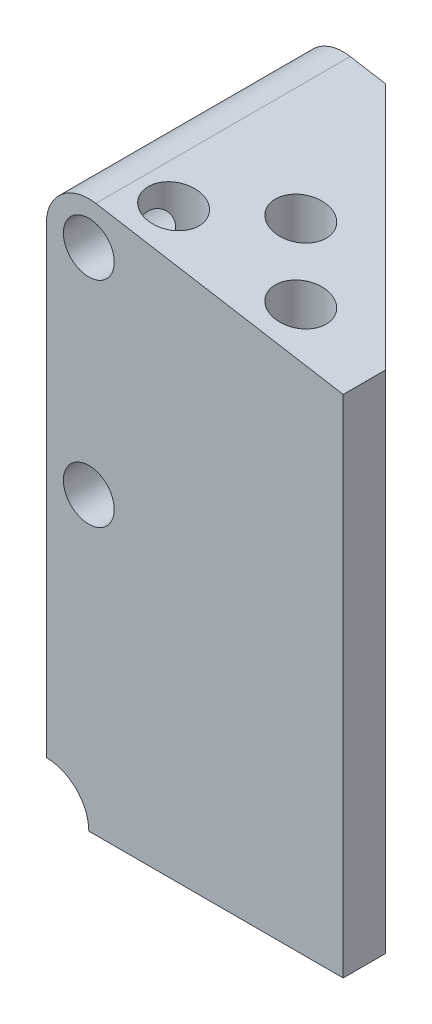
SolidWorks part; units mm, degrees
ref_plane "Front Plane" through (0, 0, 0) normal (0, 0, 1) x (1, 0, 0)
ref_plane "Top Plane" through (0, 0, 0) normal (0, 1, 0) x (1, 0, 0)
ref_plane "Right Plane" through (0, 0, 0) normal (1, 0, 0) x (0, 0, -1)
sketch "Sketch1" plane through (0, 0, 0) normal (0, 0, 1) x (1, 0, 0)
  line L0 (0, 0) -> (0, 68.7065) construction
  line L1 (-10, 130) -> (10, 130)
  line L2 (-10, 130) -> (-10, 0)
  line L3 (-10, 0) -> (10, 0)
  line L4 (10, 130) -> (10, 0)
  line L7 (0, 68.7065) -> (0, 119.2065) construction
  circle A0 centre (0, 119.2065) radius 2.5
  circle A1 centre (0, 68.7065) radius 2.5
  dimension "D2" = 5
  dimension "D3" = 68.7065
  dimension "D1" = 50.5
  dimension "D4" = 20
  dimension "D5" = 130
extrude "Boss-Extrude1" add sketch "Sketch1" along normal blind 60
sketch "Sketch2" plane through (0, 130, 0) normal (0, 1, 0) x (1, 0, 0)
  line L0 (10, 0) -> (60, -50)
  line L2 (10, -60) -> (10, 0)
  line L3 (10, -60) -> (60, -60)
  line L4 (60, -60) -> (60, -50)
  dimension "D1" = 45
  dimension "D2" = 10
extrude "Boss-Extrude2" add sketch "Sketch2" against normal up to surface (130 mm away) up to face at (0, 0, 30)
sketch "Sketch4" plane through (0, 0, 0) normal (0, 0, -1) x (-1, 0, 0)
  line L0 (-10, 68.7065) -> (-60, 68.7065)
  line L1 (10, 0) -> (10, 68.7065)
  line L2 (-10, 0) -> (10, 0)
  line L4 (-10, 130) -> (10, 130)
  line L5 (10, 130) -> (10, 119.2065)
  line L6 (10, 130) -> (10, 0) construction
  line L7 (-60, 0) -> (-60, 130) construction
  line L8 (-60, 68.7065) -> (-60, 0)
  line L9 (-60, 0) -> (-10, 0)
  line L10 (-10, 119.2065) -> (-60, 119.2065)
  line L11 (-60, 119.2065) -> (-60, 130)
  line L12 (-60, 130) -> (-10, 130)
  line L13 (-1.6667, 129.0666) -> (-60, 119.2065)
  line L14 (-1.6667, 58.8463) -> (-60, 68.7065)
  circle A0 centre (0, 119.2065) radius 10
  circle A1 centre (0, 68.7065) radius 10
  line M3 (10, 0) -> (10, 130)
  line M4 (10, 130) -> (-10, 130)
  line M5 (-10, 130) -> (-10, 0)
  line M6 (-10, 0) -> (10, 0)
extrude "Cut-Extrude2" cut sketch "Sketch4" against normal through all contours A0 L13 M3 M4 M5 | L13 L12 L11 M5 region at (-6.6017, 127.0177, 0) region at (40.3618, 126.263, 0)
extrude "Cut-Extrude3" cut sketch "Sketch4<5>" against normal blind 25 contours A1 L14 M5 M6 M3 | L14 L8 L9 M5 region at (35.5461, 32.2865, 0) region at (-0.0976, 30.0935, 0)
sketch "Sketch4<5>" plane through (0, 0, 0) normal (0, 0, -1) x (-1, 0, 0) same geometry as "Sketch4"
sketch "Sketch5" plane through (0, 0, 25) normal (0, 0, -1) x (-1, 0, 0)
  circle A0 centre (10, 0) radius 10
  dimension "D1" = 20
extrude "Cut-Extrude4" cut sketch "Sketch5" against normal through all
sketch "Sketch6" plane through (0, 0, 60) normal (0, 0, 1) x (1, 0, 0)
  circle A0 centre (0, 119.2065) radius 6
  circle A1 centre (0, 68.7065) radius 6
  dimension "D1" = 12
extrude "Cut-Extrude8" cut sketch "Sketch6" against normal offset from surface (55 mm away) 5 up to face at (2.5, 119.2065, 0)
sketch "Sketch7" plane through (0, 0, 0) normal (0, -1, 0) x (1, 0, 0)
  line L0 (25, 35) -> (10, 50) construction
  line L1 (10, 50) -> (40, 50) construction
  line L2 (40, 50) -> (25, 35) construction
  line L3 (35, 25) -> (60, 50) construction
  line L4 (40, 50) -> (40, 60) construction
  line L5 (0, 60) -> (60, 60) construction
  line L6 (25, 35) -> (25, 25) construction
  line L7 (1.6667, 25) -> (35, 25) construction
  line L8 (10, 50) -> (0, 50) construction
  line L9 (0, 60) -> (0, 25) construction
  circle A0 centre (10, 50) radius 2.5
  circle A1 centre (40, 50) radius 2.5
  circle A2 centre (25, 35) radius 2.5
  dimension "D1" = 5
  dimension "D2" = 10
extrude "Cut-Extrude9" cut sketch "Sketch7" against normal blind 5
sketch "Sketch9" plane through (0, 5, 0) normal (0, -1, 0) x (1, 0, 0)
  circle A0 centre (10, 50) radius 6
  circle A1 centre (25, 35) radius 6
  circle A2 centre (40, 50) radius 6
  circle A3 centre (25, 35) radius 2.5 construction
  dimension "D1" = 12
extrude "Cut-Extrude10" cut sketch "Sketch9" against normal through all
